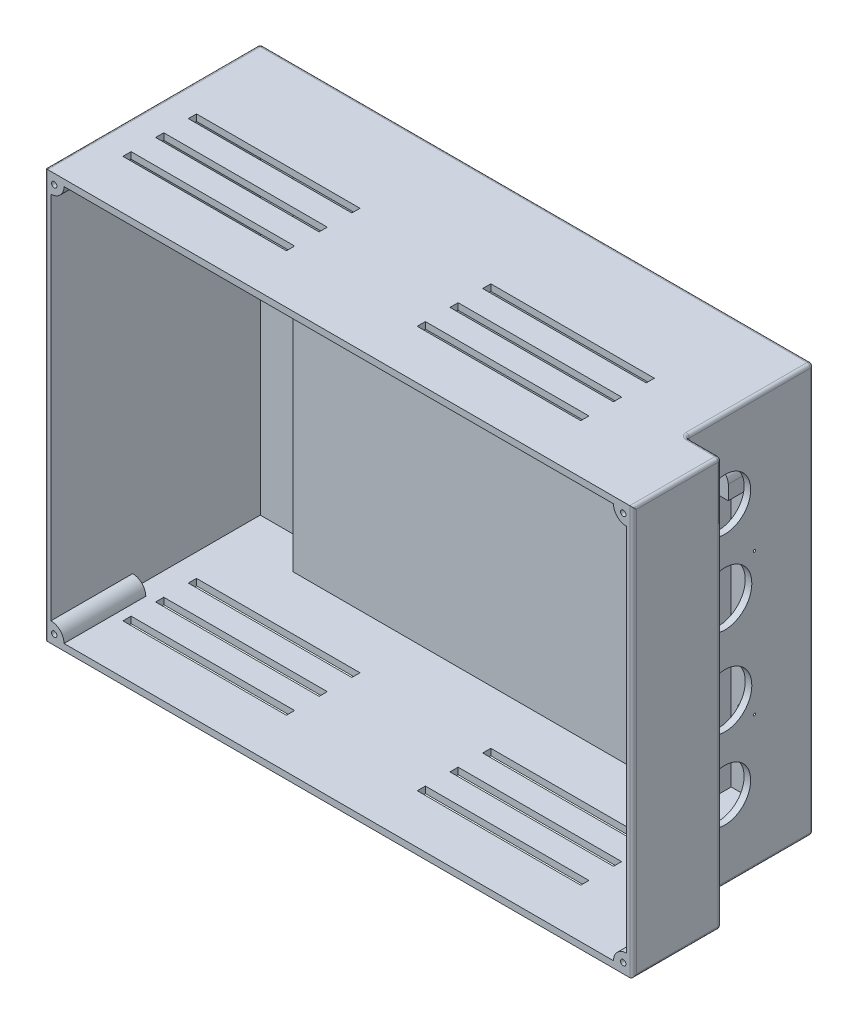
SolidWorks part; units mm, degrees
ref_plane "前视基准面" through (0, 0, 0) normal (0, 0, 1) x (1, 0, 0)
ref_plane "上视基准面" through (0, 0, 0) normal (0, 1, 0) x (1, 0, 0)
ref_plane "右视基准面" through (0, 0, 0) normal (1, 0, 0) x (0, 0, -1)
sketch "草图2" plane through (0, 0, 0) normal (0, 0, 1) x (1, 0, 0)
  line L1 (-90, 62.5) -> (90, 62.5)
  line L2 (-90, 62.5) -> (-90, -62.5)
  line L3 (-90, -62.5) -> (90, -62.5)
  line L4 (90, 62.5) -> (90, -62.5)
  line L5 (-90, 62.5) -> (90, -62.5) construction
  line L6 (-90, -62.5) -> (90, 62.5) construction
  point P0 (0, 0)
  dimension "D1" = 180
  dimension "D2" = 125
extrude "凸台-拉伸1" add sketch "草图2" along normal blind 66
sketch "草图3" plane through (0, 0, 0) normal (0, 0, -1) x (-1, 0, 0)
  line L0 (66, 59.5) -> (66, -59.5)
  line L1 (66, -59.5) -> (-54, -59.5)
  line L3 (66, 59.5) -> (-54, 59.5)
  line L4 (-54, -59.5) -> (-54, 59.5)
  line L5 (-90, 62.5) -> (90, 62.5) construction
  line L7 (90, -62.5) -> (-90, -62.5) construction
  line L9 (-90, -62.5) -> (-90, 62.5) construction
  line L11 (90, 62.5) -> (90, -62.5) construction
  dimension "D1" = 3
  dimension "D2" = 24
  dimension "D3" = 3
  dimension "D4" = 36
extrude "切除-拉伸1" cut sketch "草图3" against normal blind 10
sketch "草图4" plane through (90, 0, 0) normal (1, 0, 0) x (0, 0, -1)
  line L0 (-39, -62.5) -> (-39, 62.5)
  line L1 (-66, 61.5) -> (-66, -61.5) construction
  line L2 (-66, 62.5) -> (0, 62.5) construction
  line L4 (0, -62.5) -> (0, 62.5)
  line L6 (-66, 62.5) -> (-66, -62.5)
  line L9 (0, 62.5) -> (-39, 62.5)
  line L11 (-39, -62.5) -> (0, -62.5)
  line L14 (0, -62.5) -> (0, 62.5)
  line L15 (0, 62.5) -> (-66, 62.5)
  line L16 (-66, -62.5) -> (0, -62.5)
  dimension "D2" = 27
  dimension "D1" = 0
extrude "切除-拉伸2" cut sketch "草图4" against normal offset from surface (10.8 mm away) 2
shell "抽壳1" thickness 2 removed face at (0, 0, 66)
sketch "草图6" plane through (79.2, 0, 0) normal (1, 0, 0) x (0, 0, -1)
  line L1 (-16.0647, -23.6651) -> (-20.0647, -23.6651)
  line L2 (-16.0647, -23.6651) -> (-16.0647, -19.6651)
  line L3 (-16.0647, -19.6651) -> (-20.0647, -19.6651)
  line L4 (-20.0647, -23.6651) -> (-20.0647, -19.6651)
  line L5 (-34.2212, -23.6651) -> (-38.2212, -23.6651)
  line L6 (-34.2212, -23.6651) -> (-34.2212, -19.6651)
  line L7 (-34.2212, -19.6651) -> (-38.2212, -19.6651)
  line L8 (-38.2212, -23.6651) -> (-38.2212, -19.6651)
  line L9 (-34.2212, 19.6651) -> (-38.2212, 19.6651)
  line L10 (-34.2212, 19.6651) -> (-34.2212, 23.6651)
  line L11 (-34.2212, 23.6651) -> (-38.2212, 23.6651)
  line L12 (-38.2212, 19.6651) -> (-38.2212, 23.6651)
  line L13 (-16.0647, 19.6651) -> (-20.0647, 19.6651)
  line L14 (-16.0647, 19.6651) -> (-16.0647, 23.6651)
  line L15 (-16.0647, 23.6651) -> (-20.0647, 23.6651)
  line L16 (-20.0647, 19.6651) -> (-20.0647, 23.6651)
  arc A0 (-18.5647, 21.6651) -> (-17.5647, 21.6651) centre (-18.0647, 21.6651) ccw construction
  arc A1 (-17.5647, 21.6651) -> (-18.5647, 21.6651) centre (-18.0647, 21.6651) ccw construction
  arc A2 (-35.7212, 21.6651) -> (-36.7212, 21.6651) centre (-36.2212, 21.6651) ccw construction
  arc A3 (-36.7212, 21.6651) -> (-35.7212, 21.6651) centre (-36.2212, 21.6651) ccw construction
  arc A4 (-36.7212, -21.6651) -> (-35.7212, -21.6651) centre (-36.2212, -21.6651) ccw construction
  arc A5 (-18.5647, -21.6651) -> (-17.5647, -21.6651) centre (-18.0647, -21.6651) ccw construction
  dimension "D10" = 2
  dimension "D1" = 2
  dimension "D2" = 2
  dimension "D3" = 2
  dimension "D4" = 2
  dimension "D5" = 4
  dimension "D6" = 2
  dimension "D7" = 4
  dimension "D8" = 2
  dimension "D9" = 2
  dimension "D11" = 4
  dimension "D12" = 4
  dimension "D13" = 2
  dimension "D14" = 2
  dimension "D15" = 4
  dimension "D16" = 4
extrude "凸台-拉伸2" add sketch "草图6" against normal up to surface (3 mm away)
sketch "草图7" plane through (79.2, 0, 0) normal (1, 0, 0) x (0, 0, -1)
  circle A0 centre (-27.143, -13.5) radius 8.25
  circle A1 centre (-27.143, 13.5) radius 8.25
  circle A2 centre (-18.0647, -21.6651) radius 0.375
  circle A3 centre (-18.0647, 21.6651) radius 0.375
  circle A4 centre (-36.2212, 21.6651) radius 0.375
  circle A5 centre (-36.2212, -21.6651) radius 0.375
  arc A6 (-19.143, -13.5) -> (-35.143, -13.5) centre (-27.143, -13.5) ccw construction
  circle A7 centre (-27.143, 38.5) radius 7.9
  circle A8 centre (-27.143, 38.5) radius 7.65 construction
  circle A9 centre (-27.143, -38.5) radius 7.9
  dimension "D1" = 0.75
  dimension "D2" = 0.25
  dimension "D3" = 0.25
extrude "切除-拉伸3" cut sketch "草图7" against normal up to next
sketch "草图8" plane through (0, -62.5, 0) normal (0, -1, 0) x (1, 0, 0)
  line L0 (-90, 66) -> (90, 66) construction
  line L1 (-81, 51) -> (-31, 51)
  line L2 (-81, 51) -> (-81, 48.5)
  line L3 (-81, 48.5) -> (-31, 48.5)
  line L4 (-31, 51) -> (-31, 48.5)
  line L5 (-90, 66) -> (-90, 0) construction
  line L6 (9, 51) -> (59, 51)
  line L7 (9, 51) -> (9, 48.5)
  line L8 (9, 48.5) -> (59, 48.5)
  line L9 (59, 51) -> (59, 48.5)
  line L10 (9, 41) -> (59, 41)
  line L11 (9, 41) -> (9, 38.5)
  line L12 (9, 38.5) -> (59, 38.5)
  line L13 (59, 41) -> (59, 38.5)
  line L14 (9, 31) -> (59, 31)
  line L15 (9, 31) -> (9, 28.5)
  line L16 (9, 28.5) -> (59, 28.5)
  line L17 (59, 31) -> (59, 28.5)
  line L18 (-81, 41) -> (-31, 41)
  line L19 (-81, 41) -> (-81, 38.5)
  line L20 (-81, 38.5) -> (-31, 38.5)
  line L21 (-31, 41) -> (-31, 38.5)
  line L22 (-81, 31) -> (-31, 31)
  line L23 (-81, 31) -> (-81, 28.5)
  line L24 (-81, 28.5) -> (-31, 28.5)
  line L25 (-31, 31) -> (-31, 28.5)
  dimension "D1" = 2.5
  dimension "D2" = 15
  dimension "D3" = 9
  dimension "D4" = 50
  dimension "D5" = 2
  dimension "D6" = 3
extrude "切除-拉伸4" cut sketch "草图8" against normal up to surface (125 mm away) and the other way through all up to face at (26.4, 62.5, 35)
sketch "草图9" plane through (0, 0, 66) normal (0, 0, 1) x (1, 0, 0)
  line L1 (-88, 60.5) -> (-84, 60.5)
  line L2 (-88, 60.5) -> (-88, 56.5)
  line L5 (0, 0) -> (0, 36.715) construction
  line L6 (0, 0) -> (38.7304, 0) construction
  line L7 (-88, -60.5) -> (-88, -56.5)
  line L8 (-88, -60.5) -> (-84, -60.5)
  line L9 (88, -60.5) -> (84, -60.5)
  line L10 (88, -60.5) -> (88, -56.5)
  line L11 (88, 60.5) -> (88, 56.5)
  line L12 (88, 60.5) -> (84, 60.5)
  circle A0 centre (-87, 59.5) radius 0.825
  arc A1 (-84, 60.5) -> (-88, 56.5) centre (-88, 60.5) cw
  arc A2 (-84, -60.5) -> (-88, -56.5) centre (-88, -60.5) ccw
  circle A3 centre (-87, -59.5) radius 0.825
  circle A4 centre (87, -59.5) radius 0.825
  arc A5 (84, -60.5) -> (88, -56.5) centre (88, -60.5) cw
  arc A6 (84, 60.5) -> (88, 56.5) centre (88, 60.5) ccw
  circle A7 centre (87, 59.5) radius 0.825
  dimension "D1" = 1.65
  dimension "D2" = 1
  dimension "D3" = 1
  dimension "D4" = 4
extrude "凸台-拉伸3" add sketch "草图9" against normal up to surface (25 mm away) up to face at (82.6, 0, 41)
sketch "草图10" plane through (0, 0, 2) normal (0, 0, 1) x (1, 0, 0)
  line L0 (77.2, -60.5) -> (77.2, 60.5) construction
  line L1 (77.2, 50.5757) -> (70.499, 50.5757)
  line L2 (77.2, 50.5757) -> (77.2, 60.5)
  line L3 (77.2, 60.5) -> (70.499, 60.5)
  line L4 (70.499, 50.5757) -> (70.499, 60.5)
  line L5 (84, 60.5) -> (-84, 60.5) construction
  line L6 (56, 60.5) -> (56, -60.5) construction
  line L7 (62.513, 50.5757) -> (56, 50.5757)
  line L8 (62.513, 50.5757) -> (62.513, 60.5)
  line L9 (62.513, 60.5) -> (56, 60.5)
  line L10 (56, 50.5757) -> (56, 60.5)
  line L11 (62.513, 22.2546) -> (56, 22.2546)
  line L12 (62.513, 22.2546) -> (62.513, 29.6276)
  line L13 (62.513, 29.6276) -> (56, 29.6276)
  line L14 (56, 22.2546) -> (56, 29.6276)
  line L16 (77.2, 22.2546) -> (70.499, 22.2546)
  line L17 (77.2, 22.2546) -> (77.2, 29.6276)
  line L18 (77.2, 29.6276) -> (70.499, 29.6276)
  line L19 (70.499, 22.2546) -> (70.499, 29.6276)
  arc A0 (73.999, 27.2546) -> (73.999, 25.2546) centre (73.999, 26.2546) ccw construction
  arc A1 (59.013, 25.1276) -> (59.013, 27.1276) centre (59.013, 26.1276) ccw construction
  arc A2 (59.013, 27.1276) -> (59.013, 25.1276) centre (59.013, 26.1276) ccw construction
  arc A4 (74.126, 53.5757) -> (74.126, 55.5757) centre (74.126, 54.5757) ccw construction
  circle A5 centre (74.126, 54.5757) radius 0.825
  circle A6 centre (59.14, 54.5757) radius 0.825
  circle A7 centre (59.013, 26.1276) radius 0.825
  circle A8 centre (73.999, 26.2546) radius 0.825
  dimension "D7" = 1.65
  dimension "D6" = 1.65
  dimension "D8" = 1.65
  dimension "D9" = 1.65
  dimension "D1" = 4
  dimension "D2" = 3.5
  dimension "D3" = 3.5
  dimension "D4" = 3.5
  dimension "D5" = 4
extrude "开关螺孔凸台-拉伸4" add sketch "草图10" along normal up to surface (7.3999 mm away)
sketch "草图11" plane through (0, 0, 0) normal (0, 0, -1) x (-1, 0, 0)
  circle A0 centre (-66.76, 36.1607) radius 6.1
  circle A5 centre (-65.482, 49.2417) radius 2.6
  dimension "D1" = 12.2
  dimension "D2" = 5.2
extrude "切除-拉伸5" cut sketch "草图11" against normal up to next
fillet "圆角1" radius 3 4 edges at (62.513, 29.6276, 5.7) (62.513, 50.5757, 5.7) (70.499, 29.6276, 5.7) (70.499, 50.5757, 5.7)
fillet "圆角2" radius 1 26 edges at (90, 0, 66) (90, 0, 39) (79.2, 0, 39) (-90, 0, 66) (-90, -62.5, 33) (90, -62.5, 52.5) (84.6, -62.5, 39) (79.2, -62.5, 19.5) (-90, 62.5, 33) (79.2, 62.5, 19.5) (84.6, 62.5, 39) (90, 62.5, 52.5) (-5.4, 62.5, 0) (-90, 0, 0) (-5.4, -62.5, 0) (79.2, 0, 0) (-66, 0, 0) (-6, 59.5, 0) (54, 0, 0) (-6, -59.5, 0) (62.882, 49.2417, 0) (60.66, 36.1607, 0) (-6, 59.5, 10) (-66, 0, 10) (-6, -59.5, 10) (54, 0, 10)
